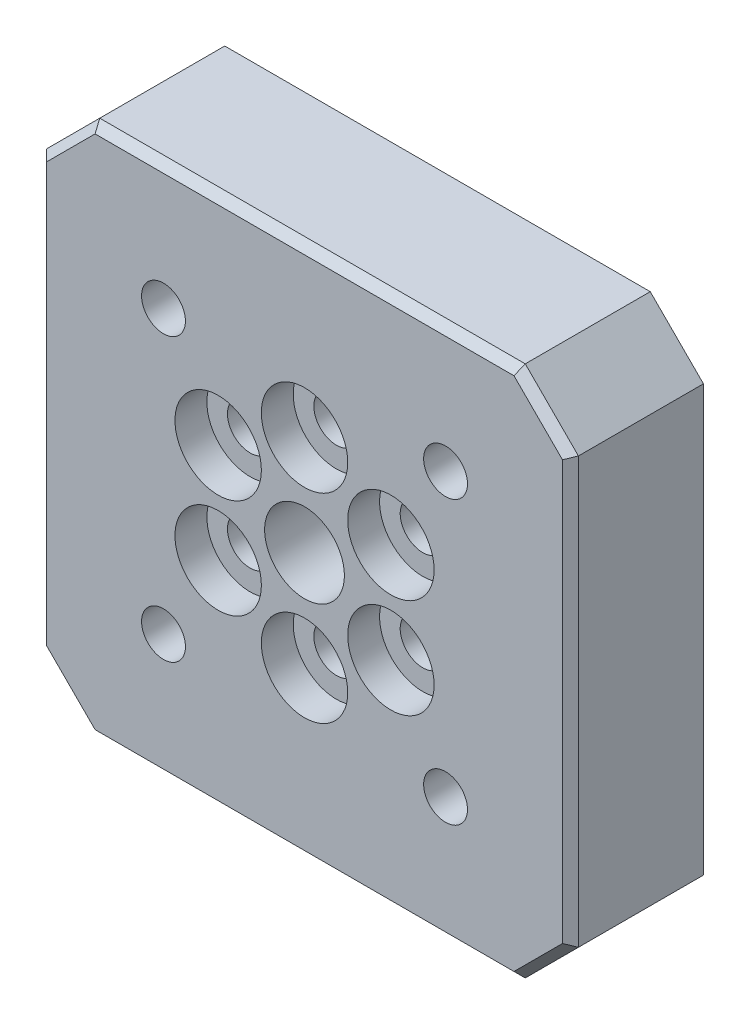
SolidWorks part; units mm, degrees
material "6061-T6 (SS)"
ref_plane "Front Plane" through (0, 0, 0) normal (0, 0, 1) x (1, 0, 0)
ref_plane "Top Plane" through (0, 0, 0) normal (0, 1, 0) x (1, 0, 0)
ref_plane "Right Plane" through (0, 0, 0) normal (1, 0, 0) x (0, 0, -1)
sketch "Sketch1" plane through (0, 0, 0) normal (0, 0, 1) x (1, 0, 0)
  line L1 (0, 0) -> (40, 0)
  line L2 (0, 0) -> (0, 40)
  line L3 (0, 40) -> (40, 40)
  line L4 (40, 0) -> (40, 40)
  dimension "D2" = 40
extrude "Boss-Extrude1" add sketch "Sketch1" along normal blind 10
sketch "Sketch18" plane through (0, 0, 10) normal (0, 0, 1) x (1, 0, 0)
  line L0 (40, 0) -> (40, 40) construction
  line L1 (0, 40) -> (0, 0) construction
  line L2 (0, 0) -> (40, 0) construction
  circle A0 centre (20, 20) radius 20
  point P1 (20, 20)
hole_wizard "Ø6.0mm Dowel Hole1" positions "Sketch18" profile "Sketch17" hole size "Ø6.0" standard "DIN" end condition through all
sketch "Sketch17" plane through (20, 20, 10) normal (1, 0, 0) x (0, -1, 0)
  line L0 (0, 0) -> (0, 10)
  line L1 (0, 10) -> (3, 10)
  line L2 (3, 10) -> (3, 0)
  line L5 (3, 0) -> (0, 0)
  line L11 (0, -6.35) -> (0, 107.95) construction
  dimension "Thru Hole Dia." = 6
  dimension "Thru Hole Depth" = 10
sketch "Sketch10" plane through (0, 0, 10) normal (0, 0, 1) x (1, 0, 0)
  point P5 (20, 27.5)
  point P12 (26.4952, 23.75)
  point P13 (26.4952, 16.25)
  point P14 (20, 12.5)
  point P15 (13.5048, 16.25)
  point P16 (13.5048, 23.75)
  dimension "D2" = 6
hole_wizard "CBORE for M3 Hex Socket Thin Head Cap Screw4" positions "Sketch10" profile "Sketch11" counterbore size "M3" standard "DIN" end condition through all
sketch "Sketch11" plane through (20, 27.5, 10) normal (1, 0, 0) x (0, -1, 0)
  line L0 (0, 0) -> (0, 10)
  line L1 (0, 10) -> (1.7, 10)
  line L3 (1.7, 10) -> (1.7, 2.4)
  line L4 (1.7, 2.4) -> (3.25, 2.4)
  line L5 (3.25, 2.4) -> (3.25, 0)
  line L7 (3.25, 0) -> (0, 0)
  line L11 (0, -6.35) -> (0, 107.95) construction
  dimension "Thru Hole Dia." = 3.4
  dimension "Thru Hole Depth" = 10
  dimension "C'Bore Dia." = 6.5
  dimension "C'Bore Depth" = 2.4
sketch "Sketch12" plane through (0, 0, 10) normal (0, 0, 1) x (1, 0, 0)
  point P4 (9.3934, 30.6066)
  point P11 (30.6066, 30.6066)
  point P12 (30.6066, 9.3934)
  point P13 (9.3934, 9.3934)
  dimension "D2" = 4
hole_wizard "Tap Drill for M4 Tap1" positions "Sketch12" profile "Sketch13" hole size "M4" standard "DIN" end condition through all
sketch "Sketch13" plane through (9.3934, 30.6066, 10) normal (1, 0, 0) x (0, -1, 0)
  line L0 (0, 0) -> (0, 10)
  line L1 (0, 10) -> (1.65, 10)
  line L2 (1.65, 10) -> (1.65, 0)
  line L5 (1.65, 0) -> (0, 0)
  line L11 (0, -6.35) -> (0, 107.95) construction
  dimension "Thru Hole Dia." = 3.3
  dimension "Thru Hole Depth" = 10
chamfer "Chamfer1" distance 4 angle 45 4 edges at (40, 0, 5) (40, 40, 5) (0, 0, 5) (0, 40, 5)
chamfer "Chamfer2" distance 0.6 angle 45 8 edges at (40, 20, 10) (38, 38, 10) (38, 2, 10) (20, 0, 10) (2, 2, 10) (0, 20, 10) (2, 38, 10) (20, 40, 10)
